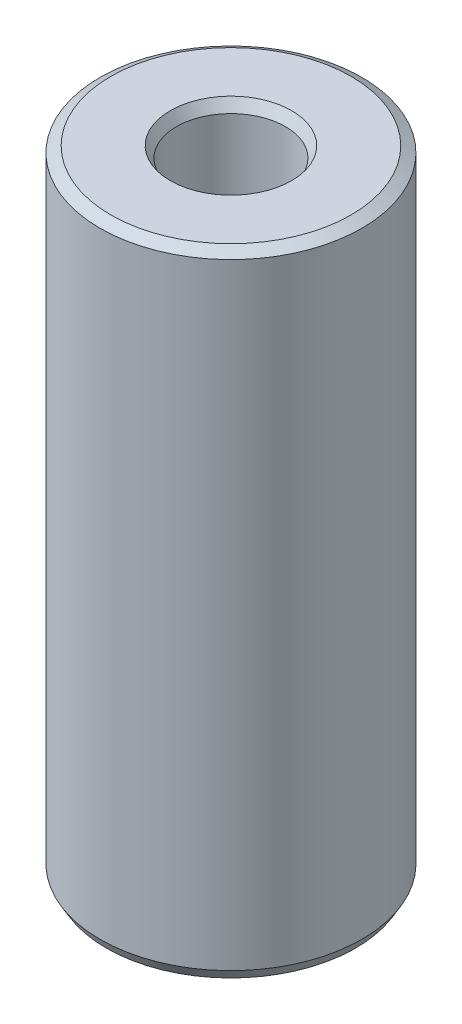
SolidWorks part; units mm, degrees
ref_plane "Front Plane" through (0, 0, 0) normal (0, 0, 1) x (1, 0, 0)
ref_plane "Top Plane" through (0, 0, 0) normal (0, 1, 0) x (1, 0, 0)
ref_plane "Right Plane" through (0, 0, 0) normal (1, 0, 0) x (0, 0, -1)
sketch "Sketch1" plane through (0, 0, 0) normal (0, 1, 0) x (1, 0, 0)
  circle A0 centre (0, 0) radius 57.5
  dimension "SLEEVE_OD" = 115
extrude "Boss-Extrude1" add sketch "Sketch1" along normal blind 278.1012
sketch "Sketch2" plane through (0, 0, 0) normal (0, 1, 0) x (1, 0, 0)
  circle A0 centre (0, 0) radius 23.9501
  dimension "BORE_D" = 47.9001
extrude "Cut-Extrude1" cut sketch "Sketch2" along normal through all
chamfer "Chamfer1" distance 2.7231 angle 60 4 edges at (0, 278.1012, 23.9501) (0, 0, 23.9501) (0, 0, 57.5) (0, 278.1012, 57.5) first distance on face at (0, 278.1012, 23.9501) first distance on face at (0, 0, 23.9501) first distance on face at (0, 278.1012, 57.5)
